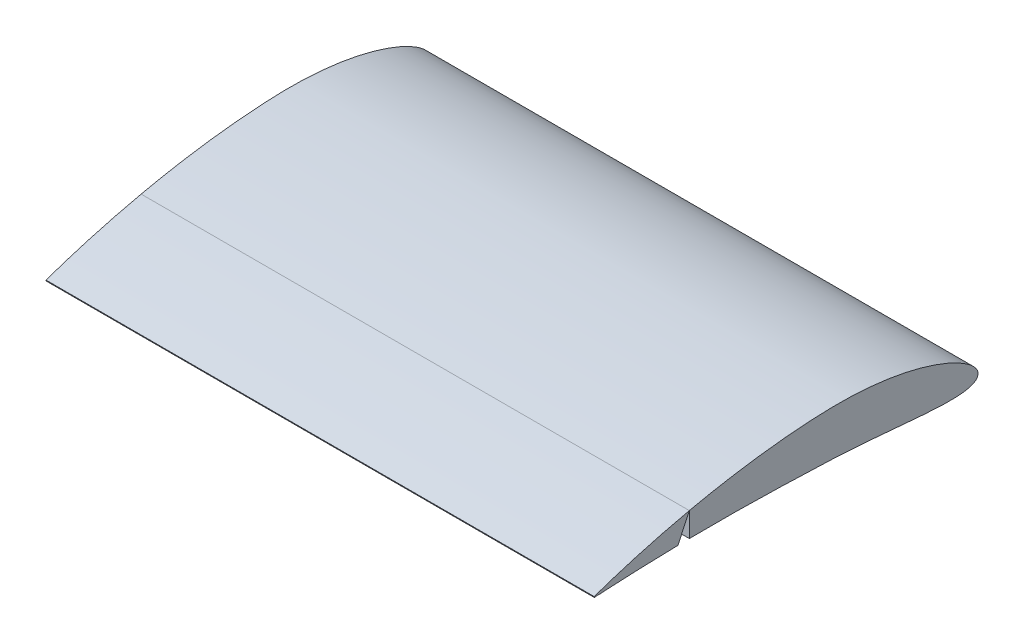
SolidWorks part; units mm, degrees
material "Thornel Mat VMA Foam Core"
ref_plane "Front Plane" through (0, 0, 0) normal (0, 0, 1) x (1, 0, 0)
ref_plane "Top Plane" through (0, 0, 0) normal (0, 1, 0) x (1, 0, 0)
ref_plane "Right Plane" through (0, 0, 0) normal (1, 0, 0) x (0, 0, -1)
curve "Curve1"
  spline degree 3 poles (0, 0.0012, 1.0003) (0, 0.0015, 0.9994) (0, 0.0028, 0.9958) (0, 0.0055, 0.9879) (0, 0.0099, 0.9747) (0, 0.0159, 0.9565) (0, 0.0233, 0.9333) (0, 0.0318, 0.9054) (0, 0.0411, 0.8731) (0, 0.051, 0.8366) (0, 0.0612, 0.7964) (0, 0.0713, 0.7528) (0, 0.0811, 0.7063) (0, 0.0903, 0.6574) (0, 0.0985, 0.6067) (0, 0.1057, 0.5546) (0, 0.1115, 0.5018) (0, 0.1158, 0.4488) (0, 0.1186, 0.3959) (0, 0.1189, 0.3436) (0, 0.1164, 0.2927) (0, 0.1112, 0.2442) (0, 0.1037, 0.1988) (0, 0.0942, 0.157) (0, 0.0831, 0.1194) (0, 0.0711, 0.0865) (0, 0.0584, 0.0585) (0, 0.0457, 0.0357) (0, 0.0334, 0.0184) (0, 0.0218, 0.0064) (0, 0.0108, -0.0005) (0, -0.0003, -0.0011) (0, -0.0092, 0.0055) (0, -0.0148, 0.017) (0, -0.0185, 0.0329) (0, -0.0204, 0.0533) (0, -0.0208, 0.0781) (0, -0.0198, 0.107) (0, -0.0176, 0.1398) (0, -0.0147, 0.176) (0, -0.0111, 0.2153) (0, -0.0074, 0.2574) (0, -0.0037, 0.3019) (0, -0.0005, 0.3484) (0, 0.002, 0.397) (0, 0.0037, 0.4471) (0, 0.0055, 0.4983) (0, 0.0069, 0.5496) (0, 0.0079, 0.6006) (0, 0.0085, 0.6505) (0, 0.0086, 0.699) (0, 0.0083, 0.7455) (0, 0.0076, 0.7894) (0, 0.0065, 0.8302) (0, 0.0053, 0.8675) (0, 0.0039, 0.9007) (0, 0.0027, 0.9296) (0, 0.0013, 0.9539) (0, 0.0006, 0.9727) (0, -0.0011, 0.9872) (0, 0, 0.9944) (0, -0.002, 0.9999) (0, -0.0005, 1) (0, 0, 1) knots 0 0 0 0 0.001372 0.005465 0.012235 0.021602 0.033461 0.047671 0.064081 0.082496 0.102719 0.124527 0.147676 0.171913 0.196978 0.222597 0.248497 0.274385 0.300041 0.32569 0.350525 0.37428 0.396711 0.417577 0.436654 0.453744 0.46868 0.481329 0.491631 0.499616 0.505546 0.510185 0.514824 0.520702 0.528516 0.538466 0.550543 0.564643 0.580638 0.598345 0.617584 0.638174 0.659922 0.682632 0.706121 0.730727 0.7557 0.780732 0.805564 0.829932 0.85357 0.876213 0.89761 0.917519 0.935698 0.951943 0.966047 0.97784 0.987174 0.993932 0.998018 0.999386 1 1 1 1
sketch "Sketch1" plane through (0, 0, 0) normal (1, 0, 0) x (0, 0, -1)
  line L0 (-354.7873, -0.0303) -> (-354.8762, 0.4104)
  line L1 (-354.7873, -0.0303) -> (0.8093, 1.5275) construction
  line L2 (0.8093, 1.5275) -> (0.7921, 5.4415) construction
  spline S1 degree 3 poles (-354.8762, 0.4104) (-354.5599, 0.5194) (-353.2997, 0.9536) (-350.4787, 1.9271) (-345.801, 3.4978) (-336.0241, 6.7216) (-319.6545, 11.7989) (-300.5983, 17.1306) (-282.4229, 21.7243) (-261.1758, 26.6516) (-238.6223, 31.1455) (-208.7748, 36.0048) (-183.9617, 39.0905) (-158.9023, 41.1132) (-140.0967, 42.1114) (-121.5167, 42.2289) (-103.4222, 41.3211) (-86.1884, 39.4787) (-70.0435, 36.8105) (-55.1998, 33.4329) (-41.8434, 29.5109) (-30.1305, 25.2201) (-20.187, 20.7343) (-12.1072, 16.2263) (-5.9269, 11.8553) (-1.6792, 7.7165) (0.7658, 3.7968) (0.9875, -0.1483) (-1.3511, -3.3089) (-5.4508, -5.2881) (-11.0873, -6.5875) (-18.3491, -7.2685) (-27.1638, -7.4049) (-37.4471, -7.0538) (-49.0831, -6.3019) (-61.9524, -5.238) (-75.9299, -3.9839) (-96.4067, -2.1536) (-117.9372, -0.4584) (-140.4848, 0.6745) (-158.2965, 1.2867) (-176.4839, 1.9179) (-200.672, 2.5862) (-224.5411, 2.9791) (-247.8302, 3.0285) (-264.3373, 2.9074) (-279.9331, 2.6564) (-294.438, 2.2829) (-307.6819, 1.8521) (-319.5134, 1.3711) (-329.7674, 0.9129) (-338.3889, 0.4268) (-345.077, 0.1915) (-350.2276, -0.4064) (-352.7802, -0.0354) (-354.7446, -0.7581) (-354.7772, -0.2025) (-354.7873, -0.0303) knots 0 0 0 0 0.001372 0.005465 0.012235 0.021602 0.047671 0.082496 0.102719 0.124527 0.171913 0.196978 0.248497 0.274385 0.300041 0.32569 0.350525 0.37428 0.396711 0.417577 0.436654 0.453744 0.46868 0.481329 0.491631 0.499616 0.505546 0.510185 0.514824 0.520702 0.528516 0.538466 0.550543 0.564643 0.580638 0.598345 0.617584 0.638174 0.682632 0.706121 0.730727 0.7557 0.780732 0.829932 0.85357 0.876213 0.89761 0.917519 0.935698 0.951943 0.966047 0.97784 0.987174 0.993932 0.998018 0.999386 1 1 1 1
  dimension "D1" = 355.6
extrude "Boss-Extrude1" add sketch "Sketch1" along normal blind 254 and the other way blind 254
sketch "Sketch2" plane through (-254, 0, 0) normal (-1, 0, 0) x (0, 0, 1)
  line L0 (266.7, 0) -> (266.7, 78.4574) construction
  line L1 (195.725, 0) -> (-195.725, 0) construction
  line L2 (0, -27.2986) -> (0, 27.2986) construction
  line L3 (266.7, 25.311) -> (266.7, 2.0657)
  line L4 (266.7, 25.311) -> (277.5394, 2.0657)
  line L5 (277.5394, 2.0657) -> (266.7, 2.0657)
  spline S0 degree 3 poles (354.7873, -0.0303) (354.7772, -0.2025) (354.7446, -0.7581) (352.7802, -0.0354) (350.2276, -0.4064) (345.077, 0.1915) (338.3889, 0.4268) (329.7674, 0.9129) (319.5134, 1.3711) (307.6819, 1.8521) (294.438, 2.2829) (279.9331, 2.6564) (264.3373, 2.9074) (247.8302, 3.0285) (224.5411, 2.9791) (200.672, 2.5862) (176.4839, 1.9179) (158.2965, 1.2867) (140.4848, 0.6745) (117.9372, -0.4584) (96.4067, -2.1536) (75.9299, -3.9839) (61.9524, -5.238) (49.0831, -6.3019) (37.4471, -7.0538) (27.1638, -7.4049) (18.3491, -7.2685) (11.0873, -6.5875) (5.4508, -5.2881) (1.3511, -3.3089) (-0.9875, -0.1483) (-0.7658, 3.7968) (1.6792, 7.7165) (5.9269, 11.8553) (12.1072, 16.2263) (20.187, 20.7343) (30.1305, 25.2201) (41.8434, 29.5109) (55.1998, 33.4329) (70.0435, 36.8105) (86.1884, 39.4787) (103.4222, 41.3211) (121.5167, 42.2289) (140.0967, 42.1114) (158.9023, 41.1132) (183.9617, 39.0905) (208.7748, 36.0048) (238.6223, 31.1455) (261.1758, 26.6516) (282.4229, 21.7243) (300.5983, 17.1306) (319.6545, 11.7989) (336.0241, 6.7216) (345.801, 3.4978) (350.4787, 1.9271) (353.2997, 0.9536) (354.5599, 0.5194) (354.8762, 0.4104) knots 0 0 0 0 0.000614 0.001982 0.006068 0.012826 0.02216 0.033953 0.048057 0.064302 0.082481 0.10239 0.123787 0.14643 0.170068 0.219268 0.2443 0.269273 0.293879 0.317368 0.361826 0.382416 0.401655 0.419362 0.435357 0.449457 0.461534 0.471484 0.479298 0.485176 0.489815 0.494454 0.500384 0.508369 0.518671 0.53132 0.546256 0.563346 0.582423 0.603289 0.62572 0.649475 0.67431 0.699959 0.725615 0.751503 0.803022 0.828087 0.875473 0.897281 0.917504 0.952329 0.978398 0.987765 0.994535 0.998628 1 1 1 1 construction
  dimension "D1" = 266.7
  dimension "D2" = 25
extrude "Cut-Extrude1" cut sketch "Sketch2" against normal up to next
sketch "Sketch3" plane through (-254, 0, 0) normal (-1, 0, 0) x (0, 0, 1)
  line L1 (195.725, 0) -> (-195.725, 0) construction
  line L2 (0, -27.2986) -> (0, 27.2986) construction
  circle A0 centre (63.5, 12.7) radius 6.35
  dimension "D1" = 12.7
  dimension "D2" = 12.7
  dimension "D3" = 63.5
extrude "Cut-Extrude2" cut sketch "Sketch3" against normal blind 101.6
sketch "Sketch4" plane through (-254, 0, 0) normal (-1, 0, 0) x (0, 0, 1)
  line L0 (195.725, 0) -> (-195.725, 0) construction
  line L1 (0, -27.2986) -> (0, 27.2986) construction
  circle A0 centre (241.3, 12.7) radius 3.175
  dimension "D1" = 6.35
  dimension "D2" = 12.7
  dimension "D3" = 241.3
extrude "Cut-Extrude3" cut sketch "Sketch4" against normal blind 127
